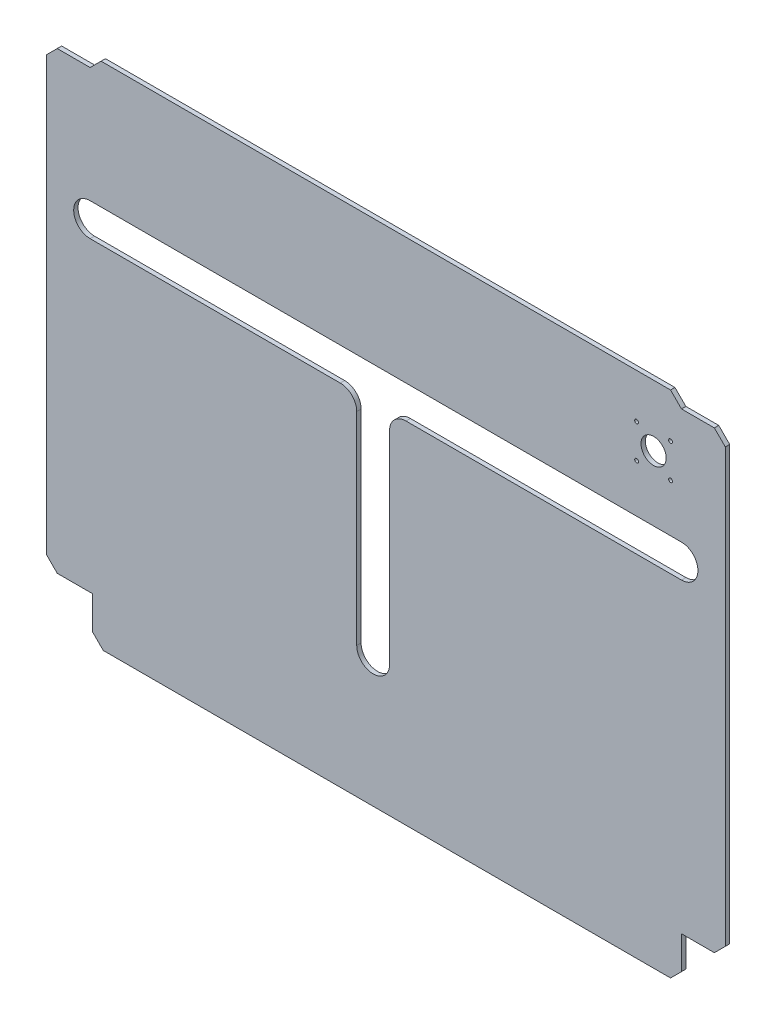
SolidWorks part; units mm, degrees
ref_plane "Front Plane" through (0, 0, 0) normal (0, 0, 1) x (1, 0, 0)
ref_plane "Top Plane" through (0, 0, 0) normal (0, 1, 0) x (1, 0, 0)
ref_plane "Right Plane" through (0, 0, 0) normal (1, 0, 0) x (0, 0, -1)
sketch "Sketch1" plane through (0, 0, 0) normal (0, 0, 1) x (1, 0, 0)
  line L0 (-39.6803, -5.0048) -> (0.3197, -5.0048)
  line L1 (0.3197, 4.9952) -> (0.3197, -5.0048)
  line L2 (540.3197, 4.9952) -> (540.3197, -5.0048)
  line L3 (2.3197, -460.0048) -> (2.3197, -420.0048)
  line L4 (540.3197, -5.0048) -> (580.3197, -5.0048)
  line L5 (540.3197, -5.0048) -> (540.3197, -420.0048) construction
  line L6 (580.3197, -5.0048) -> (580.3197, -420.0048)
  line L7 (0.3197, 4.9952) -> (540.3197, 4.9952)
  line L8 (2.3197, -460.0048) -> (540.3197, -460.0048)
  line L9 (2.3197, -420.0048) -> (-39.6803, -420.0048)
  line L10 (580.3197, -420.0048) -> (540.3197, -420.0048)
  line L11 (530.3197, -23.973) -> (530.3197, -80.4204) construction
  line L12 (-39.6803, -420.0048) -> (-39.6803, -5.0048)
  line L13 (530.3197, -35.4482) -> (499.3197, -35.4482) construction
  line L14 (540.3197, -420.0048) -> (540.3197, -460.0048)
  line L15 (499.3197, -35.4482) -> (499.3197, -66.4482) construction
  line L16 (499.3197, -66.4482) -> (530.3197, -66.4482) construction
  line L17 (530.3197, -66.4482) -> (499.3197, -35.4482) construction
  circle A0 centre (499.3197, -35.4482) radius 1.75
  circle A1 centre (499.3197, -66.4482) radius 1.75
  circle A2 centre (530.3197, -66.4482) radius 1.75
  circle A3 centre (530.3197, -35.4482) radius 1.75
  circle A4 centre (514.8197, -50.9482) radius 11.5
  dimension "D6" = 23
  dimension "D7" = 3.5
  dimension "D1" = 415
  dimension "D2" = 10
  dimension "D3" = 620
  dimension "D4" = 40
  dimension "D5" = 31
  dimension "D8" = 10
extrude "Boss-Extrude1" add sketch "Sketch1" along normal blind 4
chamfer "Chamfer1" distance 10 angle 45 2 edges at (540.3197, 4.9952, 2) (0.3197, 4.9952, 2)
chamfer "Chamfer2" distance 10 angle 45 6 edges at (580.3197, -5.0048, 2) (-39.6803, -5.0048, 2) (-39.6803, -420.0048, 2) (2.3197, -460.0048, 2) (540.3197, -460.0048, 2) (580.3197, -420.0048, 2)
sketch "Sketch2" plane through (0, 0, 4) normal (0, 0, 1) x (1, 0, 0)
  line L0 (0.3197, -110.3334) -> (540.3197, -110.3334)
  line L1 (540.3197, -140.3334) -> (0.3197, -140.3334)
  line L2 (12.3197, -460.0048) -> (530.3197, -460.0048) construction
  line L4 (530.3197, 4.9952) -> (10.3197, 4.9952) construction
  arc A0 (0.3197, -110.3334) -> (0.3197, -140.3334) centre (0.3197, -125.3334) ccw
  arc A1 (540.3197, -140.3334) -> (540.3197, -110.3334) centre (540.3197, -125.3334) ccw
  point P8 (270.3197, -140.3334)
  point P11 (270.3197, 4.9952)
  dimension "D2" = 15
  dimension "D1" = 540
  dimension "D3" = 0
extrude "Cut-Extrude1" cut sketch "Sketch2" against normal blind 10
sketch "Sketch3" plane through (0, 0, 0) normal (0, 0, -1) x (-1, 0, 0)
  line L0 (-273.7635, -140.3334) -> (-273.7635, -340.3334)
  line L1 (-0.3197, -140.3334) -> (-540.3197, -140.3334) construction
  line L2 (-243.7635, -340.3334) -> (-243.7635, -140.3334)
  line L3 (-243.7635, -140.3334) -> (-273.7635, -140.3334)
  arc A0 (-273.7635, -340.3334) -> (-243.7635, -340.3334) centre (-258.7635, -340.3334) ccw
  dimension "D2" = 15
  dimension "D1" = 200
extrude "Cut-Extrude2" cut sketch "Sketch3" against normal blind 10
fillet "Fillet1" radius 15 2 edges at (243.7635, -140.3334, 2) (273.7635, -140.3334, 2)
